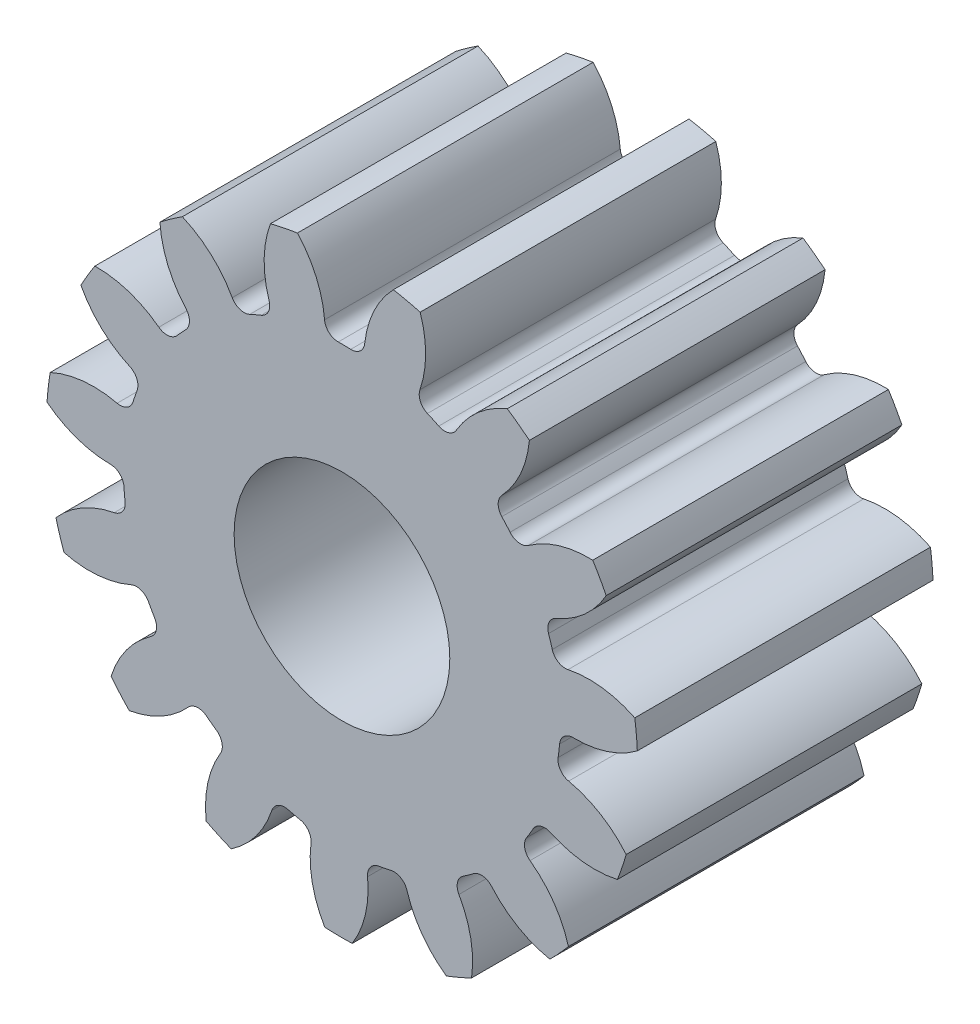
SolidWorks part; units mm, degrees
material "Delrin 2700 NC010, Low Viscosity Acetal Copolymer (SS)"
ref_plane "Front" through (0, 0, 0) normal (0, 0, 1) x (1, 0, 0)
ref_plane "Top" through (0, 0, 0) normal (0, 1, 0) x (1, 0, 0)
ref_plane "Right" through (0, 0, 0) normal (1, 0, 0) x (0, 0, -1)
sketch "Sketch3" plane through (0, 0, 0) normal (0, 0, 1) x (1, 0, 0)
  circle A0 centre (0, 0) radius 21.59
  dimension "od" = 43.18
extrude "gearBody" add sketch "Sketch3" along normal blind 25.4
sketch "Sketch2" plane through (0, 0, 0) normal (0, 0, 1) x (1, 0, 0)
  line L0 (0, 0) -> (17.0393, 7.0579) construction
  line L1 (22.0105, -8.0941) -> (0, 0) construction
  line L2 (0, 0) -> (36.3143, 0) construction
  line L3 (19.0486, -0.229) -> (18.5878, -4.1711) construction
  line L5 (18.8182, -2.2) -> (0, 0) construction
  line L7 (0, 0) -> (18.4432, 0) construction
  arc A0 (18.4395, -0.3701) -> (18.0276, -3.8932) centre (0, 0) ccw construction
  arc A1 (21.5666, 1.0048) -> (20.7532, -5.9524) centre (0, 0) ccw construction
  arc A2 (19.0486, -0.229) -> (18.5878, -4.1711) centre (0, 0) ccw construction
  arc A3 (15.7838, -2.3046) -> (15.8898, -1.3984) centre (0, 0) ccw
  arc A4 (22.0105, -8.0941) -> (16.5506, -3.4102) centre (14.9518, -10.798) ccw
  arc A5 (22.0105, -8.0941) -> (23.2839, 2.7987) centre (0, 0) ccw
  arc A6 (23.2839, 2.7987) -> (16.8909, -0.4995) centre (17.0393, 7.0579) cw
  arc A7 (15.8898, -1.3984) -> (16.8909, -0.4995) centre (16.8715, -1.4848) cw
  arc A8 (16.5506, -3.4102) -> (15.7838, -2.3046) centre (16.759, -2.4469) cw
  point P6 (23.2839, 2.7987)
  point P22 (22.0105, -8.0941)
  dimension "baseDia" = 36.8864
  dimension "od" = 43.18
  dimension "pd" = 38.1
  dimension "rd" = 31.9024
  dimension "rFillet" = 0.9855
  dimension "pointX" = 23.2839
  dimension "pointY" = 2.7987
  dimension "CTT" = 3.9421
  dimension "flankCenterAngle" = 22.5
extrude "toothCut" cut sketch "Sketch2" along normal through all
pattern_circular "CirPattern1" count 15 over 360 about axis through (0, 0, 25.4) along (0, 0, -1) of "toothCut"
sketch "hub1Dia" plane through (0, 0, 0) normal (0, 0, -1) x (-1, 0, 0)
  circle A0 centre (0, 0) radius 12.7
  dimension "hub1Dia" = 25.4
sketch "hub2Dia" plane through (0, 0, 25.4) normal (0, 0, 1) x (1, 0, 0)
  circle A0 centre (0, 0) radius 12.7
  dimension "hub2dia" = 25.4
sketch "boreDia" plane through (0, 0, 0) normal (0, 0, 1) x (1, 0, 0)
  circle A0 centre (0, 0) radius 9.525
  dimension "boreDia" = 19.05
extrude "bore" cut sketch "boreDia" against normal mid plane 25400
sketch "Sketch4" plane through (0, 0, 0) normal (1, 0, 0) x (0, 0, -1)
  line L0 (-3.81, 26.192) -> (-3.81, -31.8704)
  line L1 (-3.81, 26.192) -> (8.9209, 23.4815)
  line L2 (8.9209, 23.4815) -> (6.0962, -32.4684)
  line L3 (6.0962, -32.4684) -> (-3.81, -31.8704)
  dimension "D1" = 3.81
extrude "Cut-Extrude1" cut sketch "Sketch4" against normal through all both and the other way through all
sketch "Sketch5" plane through (0, 0, 3.81) normal (0, 0, -1) x (-1, 0, 0)
  circle A0 centre (0, 0) radius 12.0533
  circle A1 centre (0, 0) radius 7.874
  dimension "D1" = 15.748
extrude "Boss-Extrude1" add sketch "Sketch5" against normal up to surface (21.59 mm away) up to face at (9.525, 0, 25.4)
